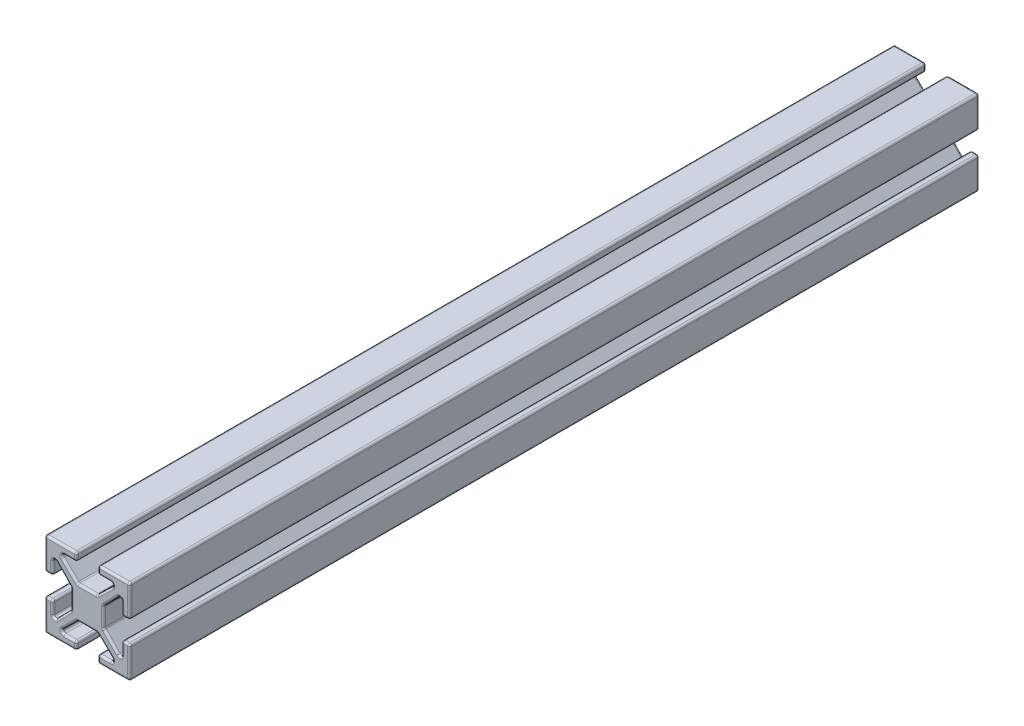
SolidWorks part; units mm, degrees
ref_plane "Front Plane" through (0, 0, 0) normal (0, 0, 1) x (1, 0, 0)
ref_plane "Top Plane" through (0, 0, 0) normal (0, 1, 0) x (1, 0, 0)
ref_plane "Right Plane" through (0, 0, 0) normal (1, 0, 0) x (0, 0, -1)
sketch "Sketch1" plane through (0, 0, 0) normal (0, 0, 1) x (1, 0, 0)
  line L0 (-5, 20) -> (-5, 16.2126)
  line L1 (-20, -20) -> (20, -20)
  line L2 (-20, -20) -> (-20, 20)
  line L3 (-20, 20) -> (20, 20)
  line L4 (20, -20) -> (20, 20)
  line L5 (-20, -20) -> (20, 20) construction
  line L6 (-20, 20) -> (20, -20) construction
  line L7 (-5, 16.2126) -> (-13.4323, 16.2126)
  line L8 (-13.4323, 16.2126) -> (-4.6312, 7.6894)
  line L9 (-4.6312, 7.6894) -> (0, 7.6894)
  line L10 (-7.6894, 4.6312) -> (-7.6894, 0)
  line L11 (-16.2126, 13.4323) -> (-7.6894, 4.6312)
  line L12 (-16.2126, 5) -> (-16.2126, 13.4323)
  line L13 (-20, 5) -> (-16.2126, 5)
  line L14 (0, 7.6894) -> (0, 16.8611) construction
  line L15 (0, 0) -> (-11.384, 0) construction
  line L16 (5, 20) -> (5, 16.2126)
  line L17 (5, 16.2126) -> (13.4323, 16.2126)
  line L18 (13.4323, 16.2126) -> (4.6312, 7.6894)
  line L19 (16.2126, 13.4323) -> (7.6894, 4.6312)
  line L20 (16.2126, 5) -> (16.2126, 13.4323)
  line L21 (20, 5) -> (16.2126, 5)
  line L22 (7.6894, 4.6312) -> (7.6894, 0)
  line L23 (4.6312, 7.6894) -> (0, 7.6894)
  line L24 (20, -5) -> (16.2126, -5)
  line L25 (16.2126, -5) -> (16.2126, -13.4323)
  line L26 (16.2126, -13.4323) -> (7.6894, -4.6312)
  line L27 (13.4323, -16.2126) -> (4.6312, -7.6894)
  line L28 (5, -16.2126) -> (13.4323, -16.2126)
  line L29 (5, -20) -> (5, -16.2126)
  line L30 (4.6312, -7.6894) -> (0, -7.6894)
  line L31 (7.6894, -4.6312) -> (7.6894, 0)
  line L32 (-5, -20) -> (-5, -16.2126)
  line L33 (-5, -16.2126) -> (-13.4323, -16.2126)
  line L34 (-13.4323, -16.2126) -> (-4.6312, -7.6894)
  line L35 (-16.2126, -13.4323) -> (-7.6894, -4.6312)
  line L36 (-16.2126, -5) -> (-16.2126, -13.4323)
  line L37 (-20, -5) -> (-16.2126, -5)
  line L38 (-7.6894, -4.6312) -> (-7.6894, 0)
  line L39 (-4.6312, -7.6894) -> (0, -7.6894)
  point P0 (0, 0)
  point P52 (0, 0)
  dimension "D1" = 40
  dimension "D2" = 40
  dimension "D4" = 15
  dimension "D3" = 4
extrude "Boss-Extrude1" add sketch "Sketch1" along normal blind 400 contours L34 L39 L30 L27 L28 L29 L1 L4 L24 L25 L26 L31 L22 L19 L20 L21 L3 L16 L17 L18 L23 L9 L8 L7 L0 L2 L13 L12 L11 L10 L38 L35 L36 L37 L32 L33 region at (0, 0, 0)
fillet "Fillet3" radius 1 108 edges at (-9.0317, -11.951, 0) (0, -7.6894, 0) (9.0317, -11.951, 0) (9.2161, -16.2126, 0) (5, -18.1063, 0) (12.5, -20, 0) (20, -12.5, 0) (18.1063, -5, 0) (16.2126, -9.2161, 0) (11.951, -9.0317, 0) (7.6894, 0, 0) (11.951, 9.0317, 0) (16.2126, 9.2161, 0) (18.1063, 5, 0) (20, 12.5, 0) (5, 18.1063, 0) (9.2161, 16.2126, 0) (9.0317, 11.951, 0) (0, 7.6894, 0) (-9.0317, 11.951, 0) (-9.2161, 16.2126, 0) (-5, 18.1063, 0) (-12.5, 20, 0) (-20, 12.5, 0) (-18.1063, 5, 0) (-16.2126, 9.2161, 0) (-11.951, 9.0317, 0) (-7.6894, 0, 0) (-11.951, -9.0317, 0) (-16.2126, -9.2161, 0) (-18.1063, -5, 0) (-20, -12.5, 0) (-12.5, -20, 0) (-5, -18.1063, 0) (-9.2161, -16.2126, 0) (-9.0317, -11.951, 400) (0, -7.6894, 400) (9.0317, -11.951, 400) (9.2161, -16.2126, 400) (5, -18.1063, 400) (12.5, -20, 400) (20, -12.5, 400) (18.1063, -5, 400) (16.2126, -9.2161, 400) (11.951, -9.0317, 400) (7.6894, 0, 400) (11.951, 9.0317, 400) (16.2126, 9.2161, 400) (18.1063, 5, 400) (20, 12.5, 400) (12.5, 20, 400) (5, 18.1063, 400) (9.2161, 16.2126, 400) (9.0317, 11.951, 400) (0, 7.6894, 400) (-9.0317, 11.951, 400) (-9.2161, 16.2126, 400) (-5, 18.1063, 400) (-12.5, 20, 400) (-20, 12.5, 400) (-18.1063, 5, 400) (-16.2126, 9.2161, 400) (-11.951, 9.0317, 400) (-7.6894, 0, 400) (-11.951, -9.0317, 400) (-16.2126, -9.2161, 400) (-18.1063, -5, 400) (-20, -12.5, 400) (-12.5, -20, 400) (-5, -18.1063, 400) (-9.2161, -16.2126, 400) (-13.4323, -16.2126, 200) (-5, -16.2126, 200) (-5, -20, 200) (-20, -20, 200) (-20, -5, 200) (-16.2126, -5, 200) (-16.2126, -13.4323, 200) (-7.6894, -4.6312, 200) (-7.6894, 4.6312, 200) (-16.2126, 13.4323, 200) (-16.2126, 5, 200) (-20, 5, 200) (-20, 20, 200) (-5, 20, 200) (-5, 16.2126, 200) (-13.4323, 16.2126, 200) (-4.6312, 7.6894, 200) (4.6312, 7.6894, 200) (13.4323, 16.2126, 200) (5, 16.2126, 200) (5, 20, 200) (20, 20, 200) (20, 5, 200) (16.2126, 5, 200) (16.2126, 13.4323, 200) (7.6894, 4.6312, 200) (7.6894, -4.6312, 200) (16.2126, -13.4323, 200) (16.2126, -5, 200) (20, -5, 200) (20, -20, 200) (5, -20, 200) (5, -16.2126, 200) (13.4323, -16.2126, 200) (4.6312, -7.6894, 200) (-4.6312, -7.6894, 200) (12.5, 20, 0)
ref_plane "Plane1" through (0, 0, 200) normal (0, 0, 1) x (1, 0, 0)
